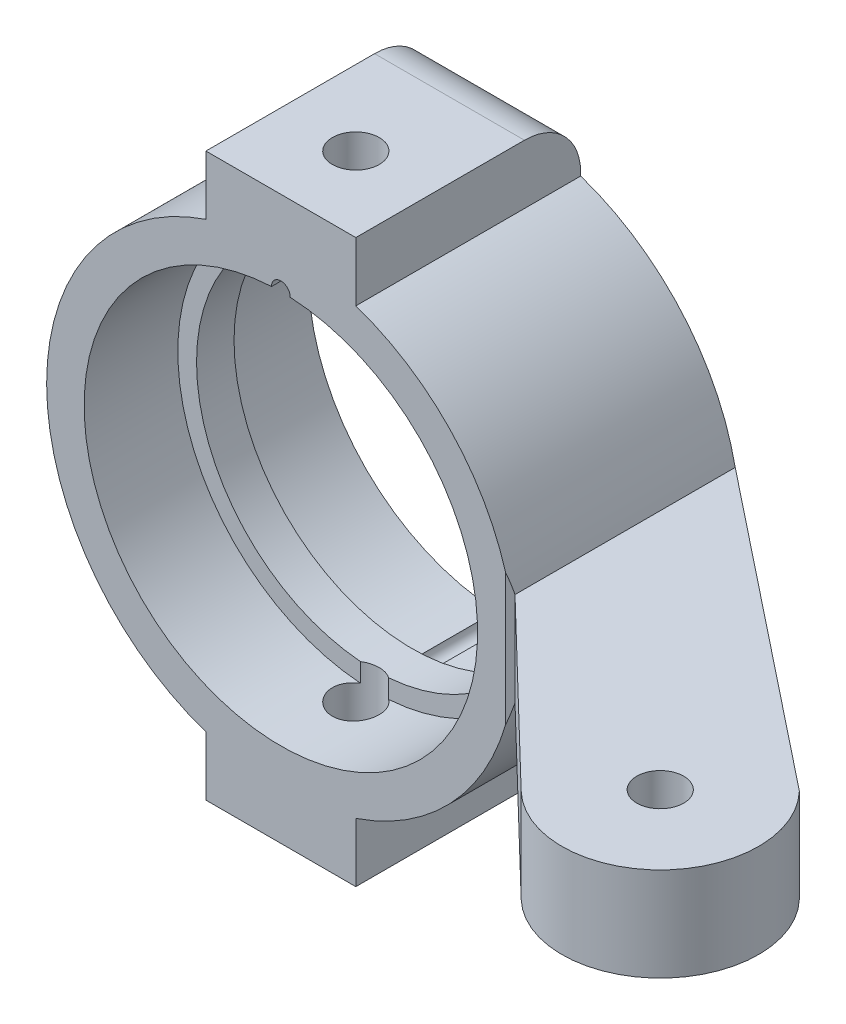
SolidWorks part; units mm, degrees
ref_plane "Front Plane" through (0, 0, 0) normal (0, 0, 1) x (1, 0, 0)
ref_plane "Top Plane" through (0, 0, 0) normal (0, 1, 0) x (1, 0, 0)
ref_plane "Right Plane" through (0, 0, 0) normal (1, 0, 0) x (0, 0, -1)
sketch "Sketch1" plane through (0, 0, 0) normal (0, 0, 1) x (1, 0, 0)
  circle A0 centre (0, 0) radius 9.5
  circle A1 centre (0, 0) radius 12.5
  dimension "D1" = 19
  dimension "D2" = 3
extrude "Boss-Extrude1" add sketch "Sketch1" along normal blind 7
sketch "Sketch2" plane through (0, 0, 7) normal (0, 0, 1) x (1, 0, 0)
  circle A0 centre (0, 0) radius 9.5
  circle A1 centre (0, 0) radius 12.5
  circle A2 centre (0, 0) radius 12.5
  dimension "D2" = 19
  dimension "D1" = 0
extrude "Boss-Extrude2" add sketch "Sketch2" along normal blind 5
sketch "Sketch3" plane through (0, 0, 0) normal (0, 1, 0) x (1, 0, 0)
  line L4 (12.5, 0) -> (-12.5, 0) construction
  line L5 (-4, 0) -> (4, 0)
  line L6 (-4, 0) -> (-4, -12)
  line L7 (-4, -12) -> (4, -12)
  line L8 (4, 0) -> (4, -12)
  line L9 (-12.5, -12) -> (12.5, -12) construction
  point P8 (0, 0)
  dimension "D1" = 8
extrude "Boss-Extrude3" add sketch "Sketch3" along normal blind 15 and the other way blind 15
sketch "Sketch4" plane through (0, 0, 12) normal (0, 0, 1) x (1, 0, 0)
  circle A0 centre (0, 0) radius 9.5
  dimension "D1" = 19
fillet "Fillet1" radius 3 2 edges at (0, -15, 0) (0, 15, 0)
sketch "Sketch6" plane through (0, 15, 0) normal (0, 1, 0) x (1, 0, 0)
  line L0 (-4, -12) -> (4, -12) construction
  circle A0 centre (0, -8) radius 1.25
  dimension "D1" = 4
  dimension "D2" = 2.5
extrude "Cut-Extrude3" cut sketch "Sketch6" against normal through all
sketch "Sketch7" plane through (4, 0, 0) normal (1, 0, 0) x (0, 0, -1)
  line L0 (-12, 9.5) -> (-12, -9.5) construction
  line L1 (-12, -2.5) -> (-2, -2.5)
  line L2 (-12, -2.5) -> (-12, 2.5)
  line L3 (-12, 2.5) -> (-2, 2.5)
  line L4 (-2, -2.5) -> (-2, 2.5)
  point P6 (-12, 0)
  dimension "D1" = 5
  dimension "D2" = 10
extrude "Boss-Extrude4" add sketch "Sketch7" along normal blind 16
chamfer "Chamfer1" distance 8 angle 45 1 edges at (20, 0, 12)
sketch "Sketch8" plane through (12, 0, 12) normal (0.7071, 0, 0.7071) x (0.7071, 0, -0.7071)
  line L1 (11.3137, -2.5) -> (0.3499, -2.5)
  line L2 (11.3137, -2.5) -> (11.3137, 2.5)
  line L3 (11.3137, 2.5) -> (0.3499, 2.5)
  line L4 (0.3499, -2.5) -> (0.3499, 2.5)
extrude "Boss-Extrude5" add sketch "Sketch8" along normal blind 18
sketch "Sketch9" plane through (0, 2.5, 0) normal (0, 1, 0) x (1, 0, 0)
  line L1 (28.8516, -20.6042) -> (25.1393, -16.8919) construction
  line L2 (32.7279, -16.7279) -> (24.9754, -24.4805) construction
  line L3 (28.9183, -13.2474) -> (20, -4)
  line L4 (20, -4) -> (32.7279, -16.7279)
  line L5 (32.7279, -16.7279) -> (24.9754, -24.4805)
  line L6 (24.9754, -24.4805) -> (12.2474, -11.7526)
  line L7 (12.2474, -11.7526) -> (21.4949, -20.6708)
  line L8 (20, -4) -> (18.0712, -2)
  line L9 (20, -2) -> (12.2474, -2) construction
  line L10 (18.0712, -2) -> (20, -2)
  line L11 (20, -2) -> (20, -4) construction
  line L12 (20, -2) -> (20, -4)
  circle A0 centre (25.1393, -16.8919) radius 1.25
  circle A1 centre (25.1393, -16.8919) radius 5.25
  line M5 (12.2474, -11.7526) -> (24.9754, -24.4805)
  line M6 (24.9754, -24.4805) -> (32.7279, -16.7279)
  line M7 (32.7279, -16.7279) -> (20, -4)
  line M8 (20, -4) -> (20, -2)
  line M9 (20, -2) -> (12.2474, -2)
  dimension "D1" = 2.5
  dimension "D2" = 4
extrude "Cut-Extrude4" cut sketch "Sketch9" against normal through all contours A1 L5 L3 M7 | A1 L7 M5 M6 | A0 | L8 M8 M9 region at (19.3571, 2.5, 2.6667) region at (24.4742, 2.5, 8.6092) region at (25.1888, 2.5, 22.3509) region at (25.1393, 2.5, 16.8919)
sketch "Sketch10" plane through (0, 2.5, 0) normal (0, 1, 0) x (1, 0, 0)
  line L0 (12.2474, -2) -> (12.2474, 0)
  line L1 (12.5, 0) -> (4, 0) construction
  line L2 (12.2474, 0) -> (18.0712, -2)
  line L3 (18.0712, -2) -> (12.2474, -2)
extrude "Boss-Extrude7" add sketch "Sketch10" against normal blind 5
sketch "Sketch11" plane through (0, 0, 0) normal (0, 0, -1) x (-1, 0, 0)
sketch "Sketch12" plane through (0, 0, 0) normal (0, 0, -1) x (-1, 0, 0)
  circle A0 centre (0, 0) radius 10.525
  dimension "D1" = 21.05
extrude "Cut-Extrude7" cut sketch "Sketch12" against normal blind 5
sketch "Sketch13" plane through (0, 0, 12) normal (0, 0, 1) x (1, 0, 0)
extrude "Cut-Extrude8" cut sketch "Sketch4" against normal through all
sketch "Sketch14" plane through (0, 0, 0) normal (0, 0, -1) x (-1, 0, 0)
  circle A0 centre (0, 10.525) radius 0.5
  circle A1 centre (0, 0) radius 10.525 construction
  circle A2 centre (0, 0) radius 10.525 construction
  circle A3 centre (0, -10.525) radius 0.5
  dimension "D1" = 1
extrude "Cut-Extrude9" cut sketch "Sketch14" against normal blind 5
sketch "Sketch15" plane through (0, 0, 12) normal (0, 0, 1) x (1, 0, 0)
  circle A0 centre (0, 0) radius 10.5
  circle A1 centre (0, 10.5) radius 0.5
  circle M2 centre (0, 0) radius 9.5
  dimension "D1" = 21
  dimension "D2" = 1
extrude "Cut-Extrude10" cut sketch "Sketch15" against normal blind 5 contours M2 | A1 A0 M2 | A0 A1 | A0 A1 region at (-7.0409, -7.3844, 12) region at (0, 10.2857, 12) region at (0, 10.71, 12) region at (0, 0, 12)
sketch "Sketch16" plane through (0, 2.5, 0) normal (0, 1, 0) x (1, 0, 0)
  line L0 (12.2474, 0) -> (28.9183, -13.2474)
  line L1 (12.2474, 0) -> (18.0712, -2)
  line L2 (18.0712, -2) -> (28.9183, -13.2474)
extrude "Cut-Extrude12" cut sketch "Sketch16" against normal blind 5
